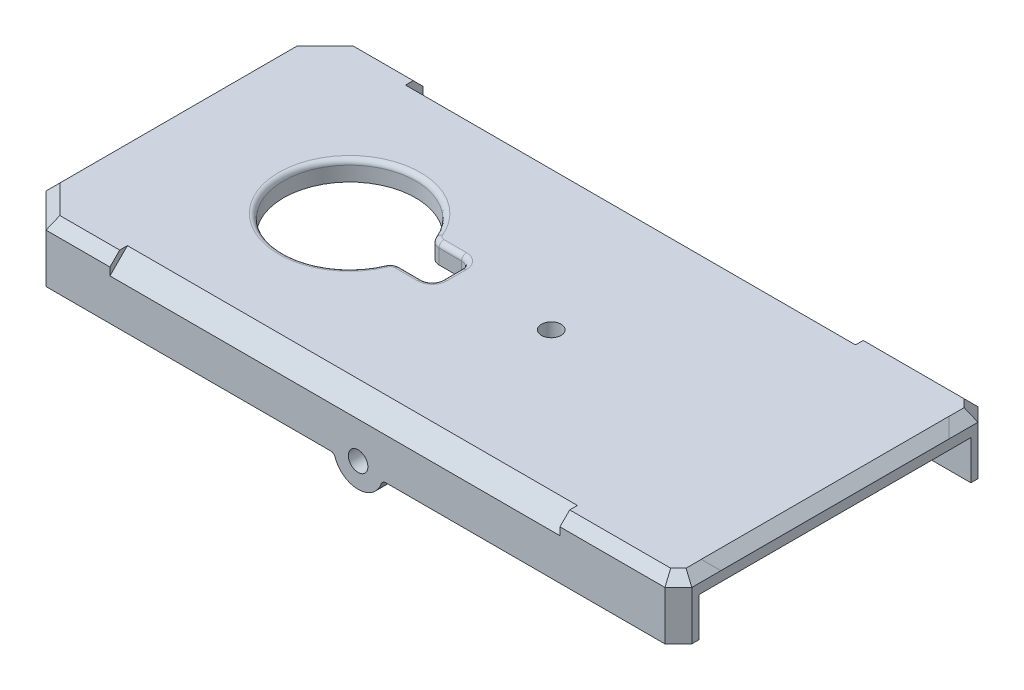
SolidWorks part; units mm, degrees
ref_plane "Front Plane" through (0, 0, 0) normal (0, 0, 1) x (1, 0, 0)
ref_plane "Top Plane" through (0, 0, 0) normal (0, 1, 0) x (1, 0, 0)
ref_plane "Right Plane" through (0, 0, 0) normal (1, 0, 0) x (0, 0, -1)
sketch "Sketch1" plane through (0, 0, 0) normal (0, 1, 0) x (1, 0, 0)
  line L0 (-9.7252, 2.4065) -> (-7.4241, 2.4065)
  line L1 (-9.7252, -1.5935) -> (-7.4241, -1.5935)
  line L2 (-6.4241, 1.4065) -> (-6.4241, -0.5935)
  line L10 (32.329, 4.4065) -> (32.329, 11.9065)
  line L11 (32.329, 11.9065) -> (30.329, 13.9065)
  line L12 (30.329, 13.9065) -> (-30.871, 13.9065)
  line L13 (-30.871, 13.9065) -> (-32.871, 11.9065)
  line L14 (-32.871, 11.9065) -> (-32.871, -11.0935)
  line L15 (-32.871, -11.0935) -> (-30.871, -13.0935)
  line L16 (-30.871, -13.0935) -> (30.329, -13.0935)
  line L17 (30.329, -13.0935) -> (32.329, -11.0935)
  line L18 (32.329, -11.0935) -> (32.329, -3.5935)
  line L19 (32.329, 4.4065) -> (32.329, -3.5935)
  line L20 (-31.9065, 16.4065) -> (-35.371, 12.942)
  line L21 (-35.371, 12.942) -> (-35.371, -12.1291)
  line L22 (-35.371, -12.1291) -> (-31.9065, -15.5935)
  line L23 (-31.9065, -15.5935) -> (31.3646, -15.5935)
  line L24 (31.3646, -15.5935) -> (34.829, -12.1291)
  line L25 (34.829, -12.1291) -> (34.829, -3.5935)
  line L26 (34.829, 4.4065) -> (34.829, -3.5935)
  line L27 (34.829, 4.4065) -> (34.829, 12.942)
  line L28 (34.829, 12.942) -> (31.3646, 16.4065)
  line L29 (31.3646, 16.4065) -> (-31.9065, 16.4065)
  line L30 (30.4947, 14.3065) -> (-31.0367, 14.3065)
  line L31 (-31.0367, 14.3065) -> (-33.271, 12.0722)
  line L32 (-33.271, 12.0722) -> (-33.271, -11.2592)
  line L33 (-33.271, -11.2592) -> (-31.0367, -13.4935)
  line L34 (-31.0367, -13.4935) -> (30.4947, -13.4935)
  line L35 (30.4947, -13.4935) -> (32.729, -11.2592)
  line L36 (32.729, -11.2592) -> (32.729, -3.5935)
  line L37 (32.729, 4.4065) -> (32.729, -3.5935)
  line L38 (32.729, 4.4065) -> (32.729, 12.0722)
  line L39 (32.729, 12.0722) -> (30.4947, 14.3065)
  arc A0 (-10.6472, 3.0194) -> (-10.6472, -2.2064) centre (-16.871, 0.4065) ccw
  arc A1 (-7.4241, -1.5935) -> (-6.4241, -0.5935) centre (-7.4241, -0.5935) ccw
  arc A2 (-7.4241, 2.4065) -> (-6.4241, 1.4065) centre (-7.4241, 1.4065) cw
  arc A3 (-10.6472, -2.2064) -> (-9.7252, -1.5935) centre (-9.7252, -2.5935) cw
  arc A4 (-9.7252, 2.4065) -> (-10.6472, 3.0194) centre (-9.7252, 3.4065) cw
  dimension "D1" = 13.5
  dimension "D2" = 1
  dimension "D3" = 2.5
  dimension "D4" = 0.4
extrude "Boss-Extrude1" add sketch "Sketch1" along normal blind 2 contours L19 L10 L11 L12 L13 L14 L15 L16 L17 L18 A4 L0 A2 L2 A1 L1 A3 A0 | L38 L39 L30 L31 L32 L33 L34 L35 L36 L37 L10 L19 L18 L17 L16 L15 L14 L13 L12 L11 region at (1.2954, 0, -0.4065) region at (31.5612, 0, -13.1387)
extrude "Boss-Extrude2" add sketch "Sketch1<3>" against normal blind 4 and the other way up to surface (2 mm away) separate body contours L28 L29 L20 L21 L22 L23 L24 L25 L26 L27 L39 L38 L37 L36 L35 L34 L33 L32 L31 L30 region at (-0.271, 0, -15.635) other way up to face at (-10.1482, 2, -0.4065)
sketch "Sketch1<3>" plane through (0, 0, 0) normal (0, 1, 0) x (1, 0, 0) same geometry as "Sketch1"
chamfer "Chamfer2" distance 1 angle 45 8 edges at (-33.6387, 2, -14.6742) (-0.271, 2, -16.4065) (33.0968, 2, -14.6742) (34.829, 2, -0.4065) (33.0968, 2, 13.8613) (-0.271, 2, 15.5935) (-33.6387, 2, 13.8613) (-35.371, 2, -0.4065)
sketch "Sketch4" plane through (0, 2, 0) normal (0, 1, 0) x (1, 0, 0)
  line L0 (32.7366, 12.1001) -> (32.7366, 15.067)
  line L2 (32.7366, 15.067) -> (34.829, 12.9746)
  line L4 (34.829, 12.9746) -> (34.829, -12.1291)
  line L7 (34.829, -12.1291) -> (32.7366, -14.2215)
  line L8 (32.7366, -14.2215) -> (32.7366, -11.2313)
  line L9 (32.7366, -11.2313) -> (32.7366, 12.1001)
  line L10 (34.829, -12.1291) -> (31.3646, -15.5935) construction
extrude "Cut-Extrude3" cut sketch "Sketch4" against normal blind 6
chamfer "Chamfer3" distance 1 angle 45 1 edges at (32.7366, 2, -0.4065)
chamfer "Chamfer4" distance 1 angle 45 1 edges at (32.729, 2, -0.4065)
sketch "Sketch5" plane through (32.7366, 0, 0) normal (1, 0, 0) x (0, 0, -1)
  line L1 (-13.4935, -4) -> (14.3065, -4)
  line L2 (-13.4935, -4) -> (-13.4935, 0)
  line L3 (-13.4935, 0) -> (14.3065, 0)
  line L4 (14.3065, -4) -> (14.3065, 0)
extrude "Cut-Extrude4" cut sketch "Sketch5" against normal blind 6
fillet "Fillet1" radius 0.5 8 edges at (-10.2788, 2, -2.5737) (-8.5746, 2, -2.4065) (-6.717, 2, -2.1136) (-6.4241, 2, -0.4065) (-6.717, 2, 1.3006) (-8.5746, 2, 1.5935) (-10.2788, 2, 1.7607) (-23.621, 2, -0.4065)
sketch "Sketch6" plane through (-35.371, 0, 0) normal (-1, 0, 0) x (0, 0, 1)
  line L0 (-14.6202, 2) -> (-16.4065, 0.2137)
  line L1 (-16.4065, 1) -> (-16.4065, -4) construction
  line L2 (-16.4065, 0.2137) -> (-16.4065, 2)
  line L3 (-16.4065, 2) -> (-14.6202, 2)
  line L4 (-0.4065, 2) -> (-0.4065, -1.8321) construction
  line L6 (-12.5278, 2) -> (11.7149, 2) construction
  line L7 (15.5935, 2) -> (13.8073, 2)
  line L8 (15.5935, 0.2137) -> (15.5935, 2)
  line L9 (13.8073, 2) -> (15.5935, 0.2137)
extrude "Cut-Extrude5" cut sketch "Sketch6" against normal blind 46 from offset 10 offset against normal yes
sketch "Sketch7" plane through (0, 0, 15.5935) normal (0, 0, 1) x (1, 0, 0)
  line L0 (-31.9065, -4) -> (31.3646, -4) construction
  circle A0 centre (0, -3.5) radius 2.5
  dimension "D1" = 5
  dimension "D2" = 0.5
extrude "Boss-Extrude3" add sketch "Sketch7" against normal up to surface (2.1 mm away) up to face at (10.7316, -0.6667, 13.4935)
fillet "Fillet2" radius 0.5 2 edges at (2.4495, -4, 14.5435) (-2.4495, -4, 14.5435)
sketch "Sketch8" plane through (-35.371, 0, 0) normal (-1, 0, 0) x (0, 0, 1)
  line L0 (-12.942, -4) -> (12.1291, -4) construction
  circle A0 centre (-0.4065, -3.5) radius 2.5
  dimension "D1" = 5
  dimension "D2" = 0.5
extrude "Boss-Extrude4" add sketch "Sketch8" against normal up to surface (2.1 mm away) up to face at (-33.271, -1, -0.4065)
fillet "Fillet3" radius 0.5 2 edges at (-34.321, -4, 2.043) (-34.321, -4, -2.856)
sketch "Sketch9" plane through (-35.371, 0, 0) normal (-1, 0, 0) x (0, 0, 1)
  circle A0 centre (-0.4065, -3.5) radius 1
  dimension "D1" = 2
extrude "Cut-Extrude6" cut sketch "Sketch9" against normal blind 46
sketch "Sketch10" plane through (0, 0, 15.5935) normal (0, 0, 1) x (1, 0, 0)
  circle A0 centre (0, -3.5) radius 1
  dimension "D1" = 2
extrude "Cut-Extrude7" cut sketch "Sketch10" against normal blind 6
sketch "Sketch11" plane through (0, 2, 0) normal (0, 1, 0) x (1, 0, 0)
  circle A0 centre (3.7434, 0.4065) radius 1
  dimension "D1" = 2
extrude "Cut-Extrude8" cut sketch "Sketch11" against normal blind 10
sketch "Sketch12" plane through (0, 0, 0) normal (0, -1, 0) x (-1, 0, 0)
  line L0 (6.4241, 1.4065) -> (6.4241, -0.5935) construction
  line L1 (10.4883, -4.5935) -> (5.4241, -4.5935)
  line L2 (10.4883, -4.5935) -> (10.4883, 5.4065)
  line L3 (10.4883, 5.4065) -> (5.4241, 5.4065)
  line L4 (5.4241, -4.5935) -> (5.4241, 5.4065)
  line L5 (9.7252, 2.4065) -> (7.4241, 2.4065) construction
  line L7 (6.4283, 5.4065) -> (10.4883, 5.4065)
  line L8 (6.4283, 5.4065) -> (6.4283, -4.5935)
  line L9 (6.4283, -4.5935) -> (10.4883, -4.5935)
  line L10 (10.4883, 5.4065) -> (10.4883, -4.5935)
  line L11 (10.4883, 5.4065) -> (5.4241, 5.4065)
  line L12 (10.4883, 5.4065) -> (10.4883, 6.1878)
  line L13 (10.4883, 6.1878) -> (5.4241, 6.1878)
  line L14 (5.4241, 5.4065) -> (5.4241, 6.1878)
  line L15 (10.4883, -4.5935) -> (5.4241, -4.5935)
  line L16 (10.4883, -4.5935) -> (10.4883, -5.3781)
  line L17 (10.4883, -5.3781) -> (5.4241, -5.3781)
  line L18 (5.4241, -4.5935) -> (5.4241, -5.3781)
  arc M4 (9.7252, 2.4065) -> (10.6472, 3.0194) centre (9.7252, 3.4065) ccw
  arc M6 (10.6472, -2.2064) -> (9.7252, -1.5935) centre (9.7252, -2.5935) ccw
  line M7 (9.7252, -1.5935) -> (7.4241, -1.5935)
  arc M8 (7.4241, -1.5935) -> (6.4241, -0.5935) centre (7.4241, -0.5935) cw
  line M9 (6.4241, -0.5935) -> (6.4241, 1.4065)
  arc M10 (6.4241, 1.4065) -> (7.4241, 2.4065) centre (7.4241, 1.4065) cw
  line M11 (7.4241, 2.4065) -> (9.7252, 2.4065)
  dimension "D1" = 1
  dimension "D2" = 10
  dimension "3" = 3
extrude "Boss-Extrude5" add sketch "Sketch12" along normal blind 4 contours L14 L3 L12 L13 | L8 L3 L4 L1 M8 M9 M10 | L1 L18 L17 L16 region at (-7.9562, 0, 4.9858) region at (-5.9258, 0, -0.4065) region at (-7.9562, 0, -5.7971)
extrude "Boss-Extrude6" add sketch "Sketch12<4>" along normal blind 2 from offset 4 contours L3 L8 L2 M10 M11 M4 | L8 L1 L2 M8 M6 M7 | L8 L3 L4 L1 M8 M9 M10 | L14 L3 L12 L13 | L8 L2 M10 M8 M7 M6 M4 M11 | L1 L18 L17 L16 | L8 M10 M9 M8 region at (-7.9562, 0, 4.9858) region at (-8.415, 0, 3.0735) region at (-5.9258, 0, -0.4065) region at (-8.525, 0, -0.4065) region at (-6.4262, 0, -0.4065) region at (-8.415, 0, -3.8864) region at (-7.9562, 0, -5.7971)
sketch "Sketch12<4>" plane through (0, 0, 0) normal (0, -1, 0) x (-1, 0, 0) same geometry as "Sketch12"
sketch "Sketch14" plane through (0, 0, 5.3781) normal (0, 0, 1) x (1, 0, 0)
  line L2 (-9.7252, 0) -> (-6.1818, 0)
  line L3 (-9.7252, 0) -> (-9.7252, -1.7285)
  line L4 (-9.7252, -1.7285) -> (-6.1818, -1.7285)
  line L5 (-6.1818, 0) -> (-6.1818, -1.7285)
extrude "Cut-Extrude9" cut sketch "Sketch14" against normal up to surface (11.5658 mm away) up to face at (-7.9562, -3, -6.1878)
